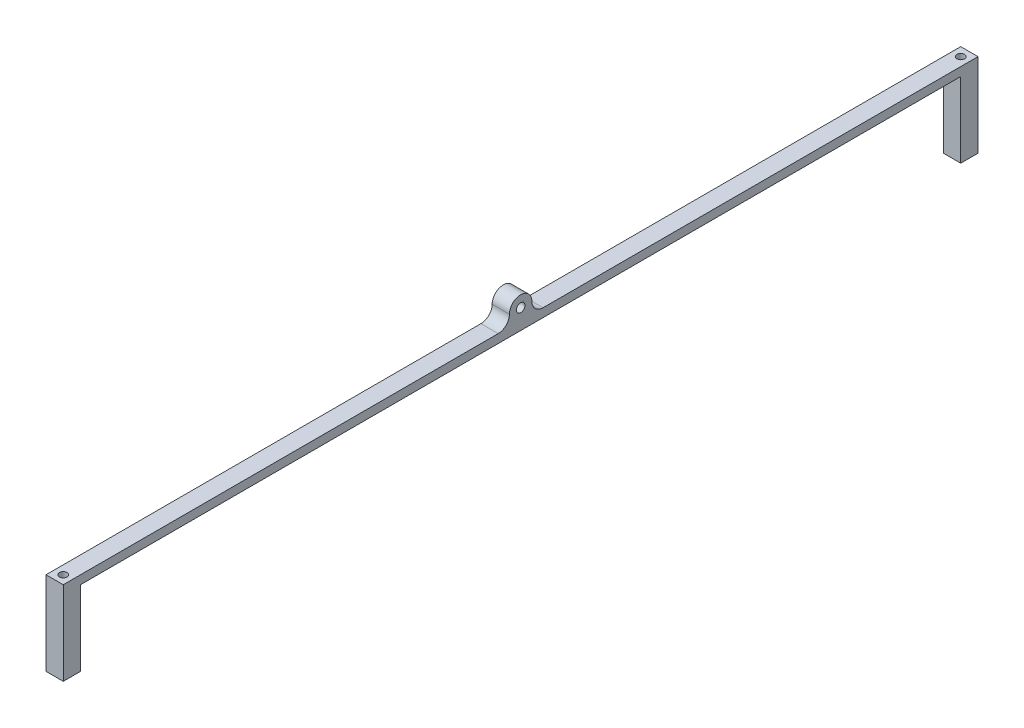
SolidWorks part; units mm, degrees
ref_plane "Спереди" through (0, 0, 0) normal (0, 0, 1) x (1, 0, 0)
ref_plane "Сверху" through (0, 0, 0) normal (0, 1, 0) x (1, 0, 0)
ref_plane "Справа" through (0, 0, 0) normal (1, 0, 0) x (0, 0, -1)
other "Configuration Table"
sketch "Эскиз1" plane through (0, 0, 0) normal (0, 1, 0) x (1, 0, 0)
  line L1 (0, 530) -> (10, 530)
  line L2 (0, 530) -> (0, 0)
  line L3 (0, 0) -> (10, 0)
  line L4 (10, 530) -> (10, 0)
  line L5 (592.3, 530) -> (592.3, 0) construction
  line L7 (0, 520) -> (10, 530) construction
  line L10 (0, 520) -> (10, 520) construction
  line L14 (0, 10) -> (10, 10) construction
  line L16 (0, 530) -> (10, 520) construction
  line L17 (0, 10) -> (10, 0) construction
  line L18 (10, 10) -> (0, 0) construction
  circle A0 centre (5, 525) radius 2.25
  circle A1 centre (5, 5) radius 2.25
  dimension "D5" = 4.5
  dimension "D6" = 4.5
  dimension "D2" = 10
  dimension "D3" = 10
  dimension "D4" = 10
extrude "Бобышка-Вытянуть1" add sketch "Эскиз1" along normal blind 5
sketch "Эскиз2" plane through (0, 0, 0) normal (1, 0, 0) x (0, 0, -1)
  line L0 (258.5, 11.5) -> (271.5, 11.5) construction
  line L1 (252, 5) -> (278, 5)
  line L2 (0, 5) -> (530, 5) construction
  arc A0 (271.5, 11.5) -> (258.5, 11.5) centre (265, 11.5) ccw
  arc A2 (252, 5) -> (258.5, 11.5) centre (252, 11.5) ccw
  arc A3 (271.5, 11.5) -> (278, 5) centre (278, 11.5) ccw
  circle A4 centre (265, 11.5) radius 2.5
  point P1 (265, 5)
  point P5 (265, 5)
  point P6 (271.5, 11.5)
  point P7 (258.5, 11.5)
  dimension "D1" = 13
  dimension "D2" = 13
  dimension "D3" = 13
  dimension "D4" = 5
extrude "Бобышка-Вытянуть2" add sketch "Эскиз2" along normal blind 10
sketch "Эскиз3" plane through (0, 0, 0) normal (0, -1, 0) x (1, 0, 0)
  line L0 (10, 0) -> (10, -530) construction
  line L1 (0, 0) -> (10, 0)
  line L2 (0, 0) -> (0, -10)
  line L3 (0, -10) -> (10, -10)
  line L4 (10, 0) -> (10, -10)
  line L6 (0, -530) -> (10, -530)
  line L7 (0, -530) -> (0, -520)
  line L8 (0, -520) -> (10, -520)
  line L9 (10, -530) -> (10, -520)
  circle A526 centre (5, -525) radius 2.25
  circle A527 centre (5, -525) radius 2.25
  circle A529 centre (5, -5) radius 2.25
  circle A530 centre (5, -5) radius 2.25
  dimension "D1" = 10
  dimension "D2" = 10
  dimension "D3" = 0
  dimension "D4" = 0
extrude "Бобышка-Вытянуть3" add sketch "Эскиз3" along normal up to surface (43.5 mm away)
